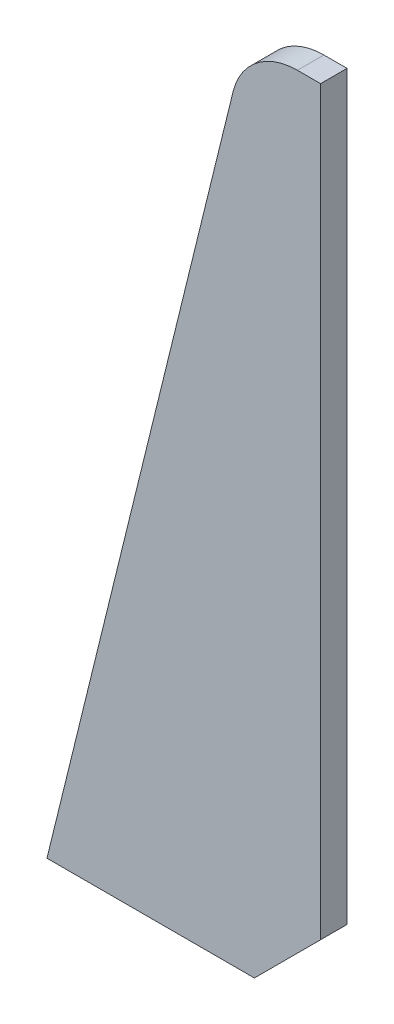
SolidWorks part; units mm, degrees
note: The reader was unsure of these and kept them because the rebuilt part matched: thickness of "Базовая кромка1", "Листовой металл3", "Листовой металл4".
material "AISI 304"
ref_plane "Спереди" through (0, 0, 0) normal (0, 0, 1) x (1, 0, 0)
ref_plane "Сверху" through (0, 0, 0) normal (0, 1, 0) x (1, 0, 0)
ref_plane "Справа" through (0, 0, 0) normal (1, 0, 0) x (0, 0, -1)
sketch "Эскиз2" plane through (0, 0, 0) normal (0, 0, 1) x (1, 0, 0)
  line L0 (-62, 0) -> (78, 0)
  line L1 (78, 0) -> (33, 183)
  line L2 (33, 183) -> (-17, 183)
  line L4 (-17, 183) -> (-62, 0)
  line L5 (8, 183) -> (8, 0) construction
  dimension "D1" = 78
  dimension "D2" = 62
  dimension "D3" = 50
  dimension "D5" = 183
base flange "Базовая кромка1" sketch "Эскиз2" thickness 6 reverse thickness direction no parameters "D1"=4
fillet "Скругление1" radius 15 2 edges at (33, 183, -3) (-17, 183, -3)
sketch "Эскиз4" plane through (0, 0, 0) normal (0, 0, 1) x (1, 0, 0)
  line L1 (0, 0) -> (94.1668, 0)
  line L2 (0, 0) -> (0, 540.1933)
  line L3 (0, 540.1933) -> (94.1668, 540.1933)
  line L4 (94.1668, 0) -> (94.1668, 540.1933)
extrude "Вырез-Вытянуть1" cut sketch "Эскиз4" against normal through all both and the other way through all normal cut yes
chamfer "Фаска1" distance 15 angle 45 1 edges at (0, 0, -3)
sketch "Сгиб-Линии1" plane through (0, 0, 0) normal (0, 1, 0) x (1, 0, 0)
sketch "Граничная рамка1" plane through (0, 0, 0) normal (0, 1, 0) x (1, 0, 0)
sheet metal parameters "Листовой металл3" thickness 6 parameters "D1"=4
flat pattern "Развертка3" [suppressed]
sketch "Сгиб-Линии2" plane through (0, 0, 0) normal (0, 1, 0) x (1, 0, 0)
sketch "Граничная рамка2" [suppressed] plane through (0, 0, 0) normal (0, 1, 0) x (1, 0, 0)
sheet metal parameters "Листовой металл4" thickness 6 parameters "D1"=4, "D7"=8
flat pattern "Развертка3"
sketch "Сгиб-Линии2" plane through (0, 0, 0) normal (0, 1, 0) x (1, 0, 0)
sketch "Граничная рамка2" [suppressed] plane through (0, 0, 0) normal (0, 1, 0) x (1, 0, 0)
